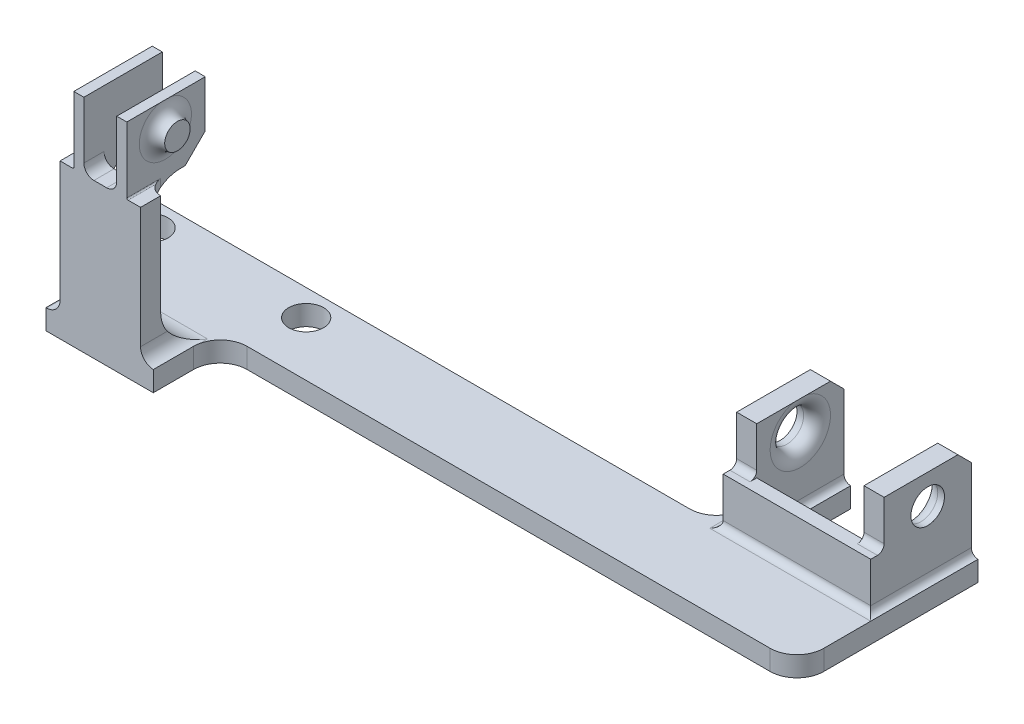
SolidWorks part; units mm, degrees
ref_plane "Alzado" through (0, 0, 0) normal (0, 0, 1) x (1, 0, 0)
ref_plane "Planta" through (0, 0, 0) normal (0, 1, 0) x (1, 0, 0)
ref_plane "Vista lateral" through (0, 0, 0) normal (1, 0, 0) x (0, 0, -1)
sketch "Croquis1" plane through (0, 0, 0) normal (0, 1, 0) x (1, 0, 0)
  line L1 (0, 0) -> (42, 0)
  line L2 (0, 0) -> (0, -8)
  line L3 (0, -8) -> (54, -8)
  line L6 (42, 0) -> (42, 1)
  line L7 (42, 1) -> (54, 1)
  line L8 (54, -8) -> (54, 1)
  circle A0 centre (3.5, -3.9) radius 2.6
  circle A1 centre (26.7, -3.9) radius 2.6
  dimension "D3" = 5.2
  dimension "D4" = 5.2
  dimension "D2" = 42
  dimension "D5" = 3.9
  dimension "D6" = 3.9
  dimension "D7" = 23.2
  dimension "D8" = 3.5
  dimension "D9" = 9
  dimension "D10" = 12
  dimension "D12" = 8
extrude "Saliente-Extruir1" add sketch "Croquis1" along normal blind 3
sketch "Croquis9" plane through (0, 3, 0) normal (0, 1, 0) x (1, 0, 0)
  line L0 (19, -8) -> (19, -12)
  line L1 (0, -8) -> (54, -8) construction
  line L2 (19, -12) -> (108, -12)
  line L3 (54, -8) -> (54, 1) construction
  line L4 (108, -12) -> (108, 15)
  line L5 (108, 15) -> (84, 15)
  line L6 (84, 15) -> (84, 0)
  line L7 (84, 0) -> (54, 0)
  line L8 (19, -8) -> (54, -8)
  line L9 (54, -8) -> (54, 0)
  dimension "D1" = 54
  dimension "D2" = 35
  dimension "D3" = 4
  dimension "D4" = 15
  dimension "D5" = 24
extrude "Saliente-Extruir7" add sketch "Croquis9" against normal up to surface (3 mm away) up to face at (32, 0, 2.3333)
sketch "Croquis10" plane through (0, 3, 0) normal (0, 1, 0) x (1, 0, 0)
  line L0 (108, 15) -> (84, 15) construction
  line L1 (85, 15) -> (88, 15)
  line L2 (85, 15) -> (85, 2)
  line L3 (85, 2) -> (88, 2)
  line L4 (88, 15) -> (88, 2)
  line L5 (84, 15) -> (84, 0) construction
  line L6 (104, 15) -> (107, 15)
  line L7 (104, 15) -> (104, 2)
  line L8 (104, 2) -> (107, 2)
  line L9 (107, 15) -> (107, 2)
  dimension "D1" = 3
  dimension "D2" = 3
  dimension "D3" = 13
  dimension "D4" = 13
  dimension "D5" = 16
  dimension "D6" = 1
extrude "Saliente-Extruir8" add sketch "Croquis10" along normal blind 14
sketch "Croquis13" plane through (107, 0, 0) normal (1, 0, 0) x (0, 0, -1)
  line L0 (15, 17) -> (15, 3) construction
  line L1 (2, 17) -> (15, 17) construction
  circle A0 centre (8.5, 12.6) radius 2.5
  dimension "D1" = 5
  dimension "D2" = 6.5
  dimension "D3" = 4.4
extrude "Cortar-Extruir2" cut sketch "Croquis13" against normal up to surface (22 mm away) up to face at (85, 10, -8.5)
sketch "Croquis14" plane through (0, 3, 0) normal (0, 1, 0) x (1, 0, 0)
  line L0 (104, 15) -> (88, 15) construction
  line L1 (89, 15) -> (103, 15)
  line L2 (89, 15) -> (89, 2)
  line L3 (89, 2) -> (103, 2)
  line L4 (103, 15) -> (103, 2)
  line L5 (88, 2) -> (88, 15) construction
  line L6 (104, 15) -> (104, 2) construction
  line L7 (104, 2) -> (107, 2) construction
  dimension "D1" = 1
  dimension "D2" = 1
  dimension "D3" = 0
extrude "Cortar-Extruir3" cut sketch "Croquis14" against normal up to surface (3 mm away) up to face at (51.1667, 0, 0.6667)
chamfer "Chaflán1" distance 2 angle 45 2 edges at (105.5, 17, -15) (86.5, 17, -15)
sketch "Croquis15" plane through (0, 3, 0) normal (0, 1, 0) x (1, 0, 0)
  line L1 (85, 2) -> (107, 2)
  line L2 (85, 2) -> (85, 0)
  line L3 (85, 0) -> (107, 0)
  line L4 (107, 2) -> (107, 0)
  dimension "D1" = 2
extrude "Saliente-Extruir11" add sketch "Croquis15" along normal blind 7
fillet "Redondeo13" radius 1 7 edges at (105.5, 10, -2) (86.5, 10, -2) (96, 3, 0) (85, 3, -7.5) (88, 3, -8.5) (104, 3, -8.5) (107, 3, -7.5)
fillet "Redondeo14" radius 2 2 edges at (88, 12.6, -6) (104, 12.6, -11)
sketch "Croquis16" plane through (0, 3, 0) normal (0, 1, 0) x (1, 0, 0)
  line L1 (0, -8) -> (19, -8)
  line L2 (0, -8) -> (0, -12)
  line L3 (0, -12) -> (6, -12)
  line L4 (19, -8) -> (19, -12)
  line L5 (19, -12) -> (22, -12)
  line L6 (6, -12) -> (6, -22)
  line L7 (6, -22) -> (22, -22)
  line L8 (22, -12) -> (22, -22)
  dimension "D1" = 16
  dimension "D2" = 6
  dimension "D3" = 4
  dimension "D4" = 10
extrude "Saliente-Extruir12" add sketch "Croquis16" against normal up to surface (3 mm away) up to face at (62.375, 0, -1.625)
sketch "Croquis17" plane through (0, 3, 0) normal (0, 1, 0) x (1, 0, 0)
  line L6 (6, -22) -> (22, -22) construction
  line L7 (8.1, -22) -> (20.1, -22)
  line L8 (8.1, -22) -> (8.1, -19)
  line L9 (8.1, -19) -> (20.1, -19)
  line L10 (20.1, -22) -> (20.1, -19)
  line L11 (22, -22) -> (22, -12) construction
  dimension "D1" = 3
  dimension "D2" = 12
  dimension "D3" = 1.9
extrude "Saliente-Extruir13" add sketch "Croquis17" along normal blind 30
sketch "Croquis18" plane through (0, 0, 19) normal (0, 0, -1) x (-1, 0, 0)
  line L0 (-20.1, 33) -> (-20.1, 3) construction
  line L1 (-8.1, 33) -> (-20.1, 33)
  line L2 (-8.1, 33) -> (-8.1, 23)
  line L3 (-8.1, 23) -> (-20.1, 23)
  line L4 (-20.1, 33) -> (-20.1, 23)
  dimension "D1" = 10
extrude "Saliente-Extruir14" add sketch "Croquis18" along normal blind 8.7
fillet "Redondeo18" radius 4 4 edges at (22, 1.5, 12) (6, 1.5, 12) (84, 1.5, 0) (108, 1.5, 12)
sketch "Croquis23" plane through (0, 3, 0) normal (0, 1, 0) x (1, 0, 0)
  line L1 (42, 1) -> (54, 1)
  line L2 (42, 1) -> (42, 0)
  line L3 (42, 0) -> (54, 0)
  line L4 (54, 1) -> (54, 0)
extrude "Cortar-Extruir6" cut sketch "Croquis23" against normal up to surface (3 mm away) up to face at (55.8935, 0, 2.8182)
sketch "Croquis24" plane through (0, 33, 0) normal (0, 1, 0) x (1, 0, 0)
  line L7 (8.1, -22) -> (20.1, -22) construction
  line L8 (20.1, -10.3) -> (18.05, -10.3)
  line L9 (20.1, -10.3) -> (20.1, -22)
  line L10 (20.1, -22) -> (18.05, -22)
  line L11 (18.05, -10.3) -> (18.05, -22)
  line L13 (8.1, -10.3) -> (10.15, -10.3)
  line L14 (8.1, -10.3) -> (8.1, -22)
  line L15 (8.1, -22) -> (10.15, -22)
  line L16 (10.15, -10.3) -> (10.15, -22)
  dimension "D1" = 2.05
  dimension "D2" = 2.05
extrude "Cortar-Extruir7" cut sketch "Croquis24" against normal blind 10
sketch "Croquis25" plane through (0, 33, 0) normal (0, 1, 0) x (1, 0, 0)
  line L0 (10.15, -10.3) -> (18.05, -10.3) construction
  line L1 (11.65, -10.3) -> (16.55, -10.3)
  line L2 (11.65, -10.3) -> (11.65, -22)
  line L3 (11.65, -22) -> (16.55, -22)
  line L4 (16.55, -10.3) -> (16.55, -22)
  line L5 (10.15, -22) -> (18.05, -22) construction
  line L6 (18.05, -10.3) -> (18.05, -22) construction
  line L7 (10.15, -22) -> (10.15, -10.3) construction
  dimension "D1" = 1.5
  dimension "D2" = 1.5
extrude "Cortar-Extruir8" cut sketch "Croquis25" against normal blind 10
sketch "Croquis26" plane through (18.05, 0, 0) normal (1, 0, 0) x (0, 0, -1)
  line L0 (-10.3, 33) -> (-22, 33) construction
  line L1 (-22, 23) -> (-22, 33) construction
  circle A0 centre (-16.25, 29.2) radius 1.9
  dimension "D1" = 3.8
  dimension "D2" = 3.8
  dimension "D3" = 5.75
extrude "Saliente-Extruir15" add sketch "Croquis26" along normal blind 1.8
sketch "Croquis27" plane through (10.15, 0, 0) normal (-1, 0, 0) x (0, 0, 1)
  line L0 (22, 23) -> (22, 33) construction
  line L1 (22, 33) -> (10.3, 33) construction
  circle A0 centre (16.25, 29.2) radius 1.9
  dimension "D1" = 3.8
  dimension "D2" = 5.75
  dimension "D3" = 3.8
extrude "Saliente-Extruir16" add sketch "Croquis27" along normal blind 1.8
fillet "Redondeo19" radius 2 2 edges at (10.15, 29.2, 14.35) (18.05, 29.2, 18.15)
fillet "Redondeo20" radius 0.2 2 edges at (10.15, 23, 20.5) (18.05, 23, 20.5)
fillet "Redondeo21" radius 1.5 2 edges at (16.55, 23, 20.5) (11.65, 23, 20.5)
fillet "Redondeo22" radius 5 3 edges at (14.1, 3, 19) (10.9, 23, 19) (17.3, 23, 19)
fillet "Redondeo23" radius 2 2 edges at (8.1, 3, 18) (20.1, 3, 18)
chamfer "Chaflán2" distance 3 angle 45 2 edges at (10.9, 23, 10.3) (17.3, 23, 10.3)
fillet "Redondeo24" radius 2 2 edges at (10.15, 20.6, 19) (18.05, 20.6, 19)
